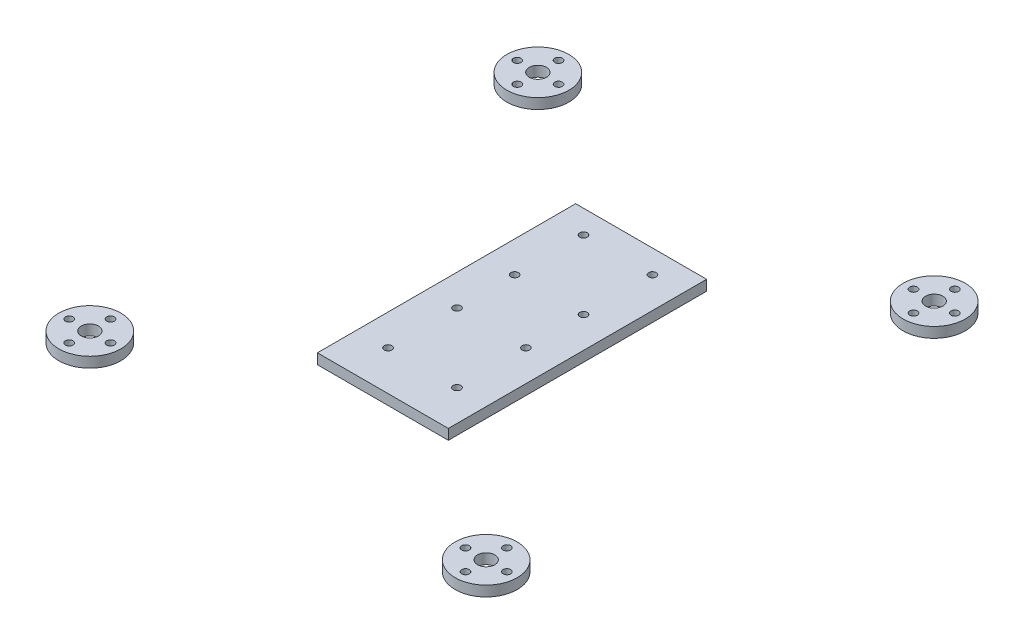
SolidWorks part; units mm, degrees
ref_plane "Front Plane" through (0, 0, 0) normal (0, 0, 1) x (1, 0, 0)
ref_plane "Top Plane" through (0, 0, 0) normal (0, 1, 0) x (1, 0, 0)
ref_plane "Right Plane" through (0, 0, 0) normal (1, 0, 0) x (0, 0, -1)
sketch "Sketch1" plane through (0, 0, 0) normal (0, 1, 0) x (1, 0, 0)
  line L0 (0, 37.475) -> (0, -37.475) construction
  line L1 (19, 37.475) -> (-19, 37.475)
  line L2 (19, 37.475) -> (19, -37.475)
  line L3 (19, -37.475) -> (-19, -37.475)
  line L4 (-19, 37.475) -> (-19, -37.475)
  line L5 (19, 37.475) -> (-19, -37.475) construction
  line L6 (19, -37.475) -> (-19, 37.475) construction
  line L8 (57.5, -65) -> (-57.5, -65)
  line L9 (57.5, -65) -> (57.5, 65)
  line L10 (57.5, 65) -> (-57.5, 65)
  line L11 (-57.5, -65) -> (-57.5, 65)
  line L12 (57.5, -65) -> (-57.5, 65) construction
  line L13 (57.5, 65) -> (-57.5, -65) construction
  line L19 (-57.5, 65) -> (0, 37.475) construction
  line L20 (-10, 30.75) -> (10, 30.75)
  line L21 (-10, 30.75) -> (-10, 10.75)
  line L22 (-10, 10.75) -> (10, 10.75)
  line L23 (10, 30.75) -> (10, 10.75)
  line L24 (-10, 30.75) -> (10, 10.75) construction
  line L25 (-10, 10.75) -> (10, 30.75) construction
  line L26 (-14.5, 5.525) -> (14.5, 5.525)
  line L27 (-14.5, 5.525) -> (-14.5, 35.975)
  line L28 (-14.5, 35.975) -> (14.5, 35.975)
  line L29 (14.5, 5.525) -> (14.5, 35.975)
  line L30 (-14.5, 5.525) -> (14.5, 35.975) construction
  line L31 (-14.5, 35.975) -> (14.5, 5.525) construction
  line L32 (-10, -5.975) -> (10, -5.975)
  line L33 (-10, -5.975) -> (-10, -25.975)
  line L34 (-10, -25.975) -> (10, -25.975)
  line L35 (10, -5.975) -> (10, -25.975)
  line L36 (-10, -5.975) -> (10, -25.975) construction
  line L37 (-10, -25.975) -> (10, -5.975) construction
  line L38 (-15.75, -35.975) -> (15.75, -35.975)
  line L39 (-15.75, -35.975) -> (-15.75, 4.025)
  line L40 (-15.75, 4.025) -> (15.75, 4.025)
  line L41 (15.75, -35.975) -> (15.75, 4.025)
  line L42 (-15.75, -35.975) -> (15.75, 4.025) construction
  line L43 (-15.75, 4.025) -> (15.75, -35.975) construction
  line L58 (-57.5, 0) -> (57.5, 0) construction
  circle A0 centre (-57.5, 65) radius 36
  circle A1 centre (-57.5, 65) radius 6
  circle A2 centre (-57.5, 65) radius 9
  circle A3 centre (-10, 30.75) radius 1.1
  circle A4 centre (10, 30.75) radius 1.1
  circle A5 centre (10, 10.75) radius 1.1
  circle A6 centre (-10, 10.75) radius 1.1
  circle A7 centre (-10, -5.975) radius 1.1
  circle A8 centre (10, -5.975) radius 1.1
  circle A9 centre (10, -25.975) radius 1.1
  circle A10 centre (-10, -25.975) radius 1.1
  circle A11 centre (-57.5, 71) radius 1.1
  circle A12 centre (-63.5, 65) radius 1.1
  circle A13 centre (-57.5, 59) radius 1.1
  circle A14 centre (-51.5, 65) radius 1.1
  circle A15 centre (57.5, 59) radius 1.1
  circle A16 centre (51.5, 65) radius 1.1
  circle A17 centre (57.5, 71) radius 1.1
  circle A18 centre (63.5, 65) radius 1.1
  circle A19 centre (57.5, 65) radius 9
  circle A20 centre (57.5, -65) radius 9
  circle A21 centre (51.5, -65) radius 1.1
  circle A22 centre (57.5, -59) radius 1.1
  circle A23 centre (63.5, -65) radius 1.1
  circle A24 centre (57.5, -71) radius 1.1
  circle A25 centre (-57.5, -59) radius 1.1
  circle A26 centre (-51.5, -65) radius 1.1
  circle A27 centre (-57.5, -71) radius 1.1
  circle A28 centre (-63.5, -65) radius 1.1
  circle A29 centre (-57.5, -65) radius 9
  circle A30 centre (-57.5, -65) radius 36
  circle A31 centre (57.5, 65) radius 36
  circle A32 centre (57.5, -65) radius 36
  circle A33 centre (-57.5, 65) radius 2.5
  circle A34 centre (57.5, 65) radius 2.5
  circle A35 centre (57.5, -65) radius 2.5
  circle A36 centre (-57.5, -65) radius 2.5
  point P0 (0, 0)
  point P8 (0, 0)
  point P16 (0, 20.75)
  point P18 (0, 0)
  point P20 (0, 0)
  point P21 (0, 0)
  point P26 (0, 20.75)
  point P31 (0, -15.975)
  point P36 (0, -15.975)
  dimension "D3" = 72
  dimension "D4" = 12
  dimension "D5" = 3
  dimension "D17" = 2.2
  dimension "D19" = 5
  dimension "D2" = 1.5
  dimension "D6" = 115
  dimension "D7" = 130
  dimension "D8" = 3.25
  dimension "D10" = 20
  dimension "D11" = 29
  dimension "D12" = 30.45
  dimension "D13" = 40
  dimension "D14" = 31.5
  dimension "D15" = 1.5
  dimension "D16" = 1.5
extrude "Boss-Extrude1" add sketch "Sketch1" along normal blind 3 contours A2 | A11 | A14 | A13 | A12 | A19 | A15 | A18 | A17 | A16 | L1 L4 L3 L2 | A29 | A27 | A28 | A25 | A26 | A20 | A24 | A21 | A22 | A23 | A4 | A3 | A7 | A8 | A9 | A10 | A5 | A6 | A33 | A34 | A35 | A36
